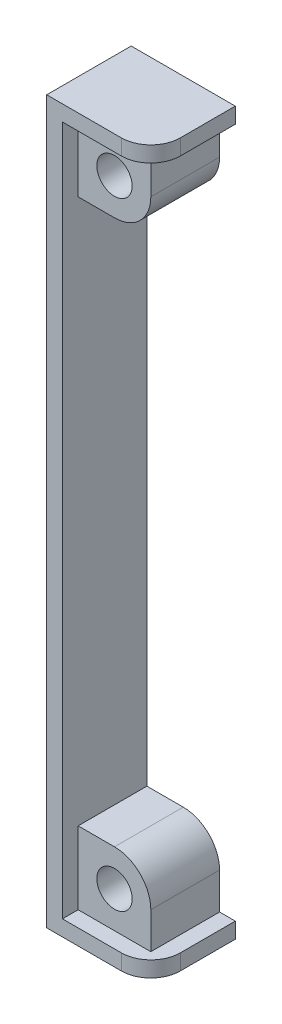
SolidWorks part; units mm, degrees
ref_plane "Спереди" through (0, 0, 0) normal (0, 0, 1) x (1, 0, 0)
ref_plane "Сверху" through (0, 0, 0) normal (0, 1, 0) x (1, 0, 0)
ref_plane "Справа" through (0, 0, 0) normal (1, 0, 0) x (0, 0, -1)
sketch "Эскиз1" plane through (0, 0, 0) normal (0, 0, 1) x (1, 0, 0)
  line L0 (5.3, 0) -> (5.3, 73.465) construction
  line L13 (0, 0) -> (10.6, 0)
  line L14 (0, 0) -> (0, 73.465)
  line L15 (0, 73.465) -> (10.6, 73.465)
  line L16 (10.6, 0) -> (10.6, 73.465)
  line L17 (1.6, 73.465) -> (1.6, 0)
  line L18 (1.6, 1.6) -> (10.6, 1.6)
  line L19 (1.6, 71.865) -> (10.6, 71.865)
  line L20 (9, 5.3) -> (9, 1.6)
  line L21 (5.3, 9) -> (1.6, 9)
  line L22 (5.3, 64.465) -> (1.6, 64.465)
  line L23 (9, 68.165) -> (9, 71.865)
  circle A0 centre (5.3, 68.165) radius 1.8
  circle A1 centre (5.3, 5.3) radius 1.8
  circle A2 centre (5.3, 68.165) radius 3.7
  circle A3 centre (5.3, 5.3) radius 3.7
  dimension "D8" = 3.6
  dimension "D9" = 3.6
  dimension "D1" = 1.6
  dimension "D2" = 3.7
  dimension "D3" = 3.7
  dimension "D4" = 3.7
  dimension "D5" = 1.6
  dimension "D6" = 1.6
  dimension "D7" = 62.865
extrude "Бобышка-Вытянуть1" add sketch "Эскиз1" along normal blind 7 contours A2 L17 L22 | A2 L19 L17 | L0 A2 A0 | A2 L0 A0 | A2 L23 L19 | A3 L18 L20 | A3 L17 L18 | A3 L21 L17 | A3 L0 A1 | L0 A3 A1 region at (7.1203, 5.3, 0) region at (2.4265, 8.1735, 0) region at (3.4797, 5.3, 0) region at (3.4797, 68.165, 0) region at (7.1203, 68.165, 0) region at (2.4265, 65.2915, 0) region at (8.1735, 2.4265, 0) region at (2.4265, 2.4265, 0) region at (8.1735, 71.0385, 0) region at (2.4265, 71.0385, 0)
extrude "Бобышка-Вытянуть2" add sketch "Эскиз1<3>" along normal blind 8.6 contours L0 L13 L16 L18 | L13 L0 L18 L17 | L17 L15 L14 L13 | L19 L0 L15 L17 | L0 L19 L16 L15 region at (0.8, 36.7325, 0) region at (7.95, 0.8, 0) region at (3.45, 0.8, 0) region at (7.95, 72.665, 0) region at (3.45, 72.665, 0)
sketch "Эскиз1<3>" plane through (0, 0, 0) normal (0, 0, 1) x (1, 0, 0) same geometry as "Эскиз1"
fillet "Скругление1" radius 3 2 edges at (10.6, 0.8, 8.6) (10.6, 72.665, 8.6)
